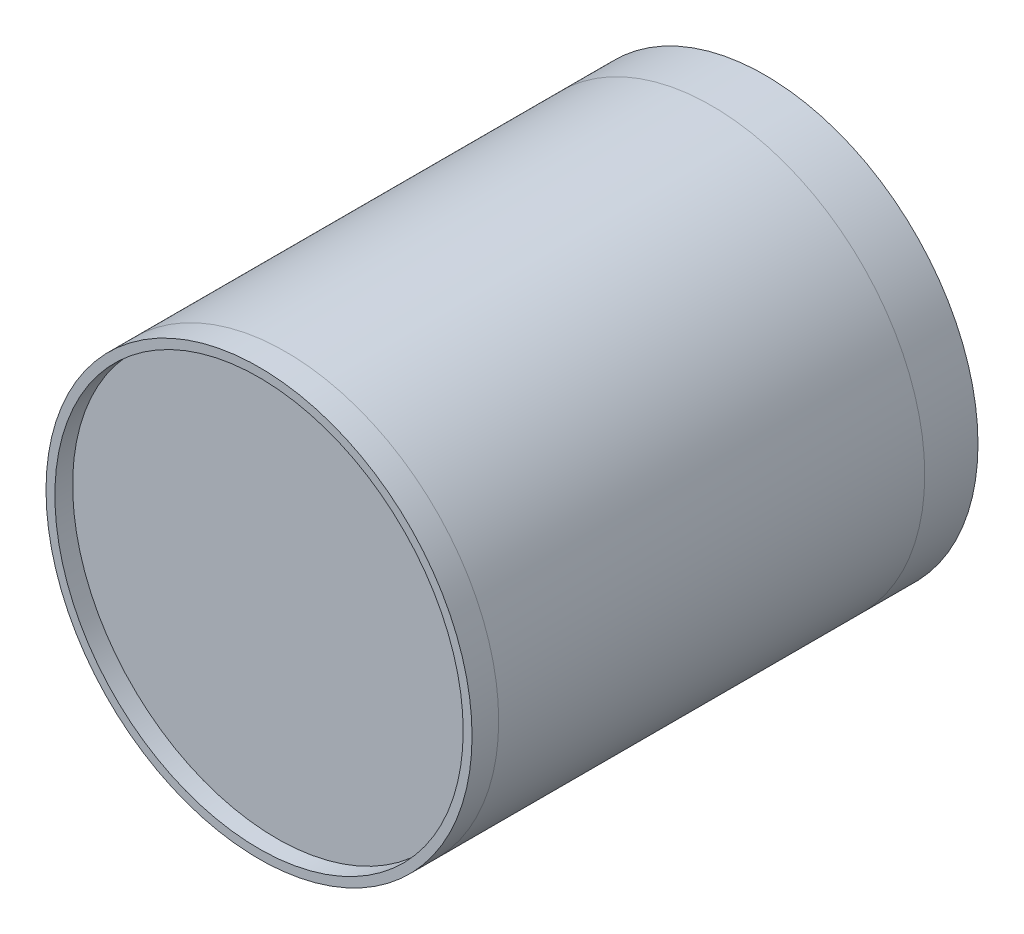
SolidWorks part; units mm, degrees
ref_plane "Front Plane" through (0, 0, 0) normal (0, 0, 1) x (1, 0, 0)
ref_plane "Top Plane" through (0, 0, 0) normal (0, 1, 0) x (1, 0, 0)
ref_plane "Right Plane" through (0, 0, 0) normal (1, 0, 0) x (0, 0, -1)
sketch "Sketch1" plane through (0, 0, 0) normal (0, 0, 1) x (1, 0, 0)
  circle A0 centre (0, 0) radius 609.6
  dimension "D1" = 1219.2
extrude "Boss-Extrude1" add sketch "Sketch1" against normal blind 152.4
sketch "Sketch5" plane through (0, 0, 0) normal (0, 0, 1) x (1, 0, 0)
  circle A0 centre (0, 0) radius 76.2
  circle A1 centre (0, 0) radius 25.4
  point P3 (0, 0)
  point P4 (0, 0)
  dimension "D1" = 152.4
  dimension "D2" = 50.8
extrude "Boss-Extrude5" add sketch "Sketch5" along normal blind 25.4 contours A1 | A0 A1 region at (-74.0447, 0, 0) region at (0, 0, 0)
extrude "Boss-Extrude6" add sketch "Sketch5<3>" along normal blind 50.8 contours A1 region at (0, 0, 0)
sketch "Sketch5<3>" plane through (0, 0, 0) normal (0, 0, 1) x (1, 0, 0) same geometry as "Sketch5"
sketch "Sketch2" plane through (0, 0, 0) normal (0, 0, 1) x (1, 0, 0)
  circle A0 centre (0, 0) radius 609.6 construction
  circle A1 centre (0, 0) radius 609.6
  circle A2 centre (0, 0) radius 603.25
  circle M3 centre (0, 0) radius 609.6
  dimension "D1" = 6.35
extrude "Boss-Extrude2" add sketch "Sketch2" along normal blind 1219.2 separate body contours A2 M3 region at (-607.8758, 0, 0)
sketch "Sketch3" plane through (0, 0, 1219.2) normal (0, 0, 1) x (1, 0, 0)
  circle A0 centre (0, 0) radius 609.6 construction
  circle A1 centre (0, 0) radius 609.6
extrude "Boss-Extrude3" add sketch "Sketch3" along normal blind 76.2 separate body
sketch "Sketch4" plane through (0, 0, 1295.4) normal (0, 0, 1) x (1, 0, 0)
  circle A2 centre (0, 0) radius 584.2
  circle A3 centre (0, 0) radius 584.2
  dimension "D1" = 25.4
extrude "Cut-Extrude1" cut sketch "Sketch4" against normal offset from surface (50.8 mm away) 25.4 up to face at (609.6, 0, 1219.2)
